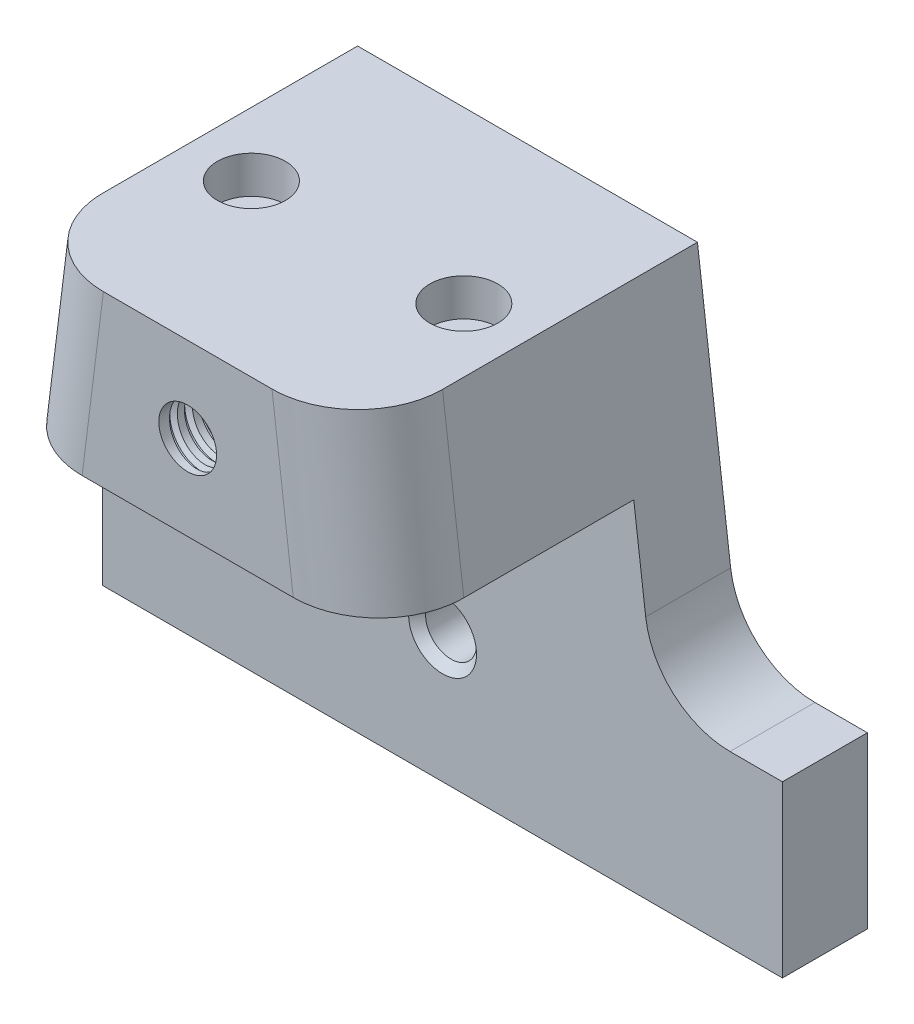
SolidWorks part; units mm, degrees
material "6063-T1"
ref_plane "Front" through (0, 0, 0) normal (0, 0, 1) x (1, 0, 0)
ref_plane "Top" through (0, 0, 0) normal (0, 1, 0) x (1, 0, 0)
ref_plane "Right" through (0, 0, 0) normal (1, 0, 0) x (0, 0, -1)
sketch "Schizzo4" plane through (0, 0, 0) normal (1, 0, 0) x (0, 0, -1)
  line L0 (0, 0) -> (-10, 0)
  line L1 (-10, 0) -> (-10, 40)
  line L2 (-10, 40) -> (-40, 40)
  line L3 (-40, 40) -> (-40, 60)
  line L4 (-40, 60) -> (0, 60)
  line L5 (0, 60) -> (0, 0)
  dimension "D1" = 10
  dimension "D2" = 40
  dimension "D3" = 30
  dimension "D4" = 20
extrude "Estrusione-Estrusione2" add sketch "Schizzo4" along normal mid plane 80
sketch "Schizzo5" plane through (0, 0, 40) normal (0, 0, 1) x (1, 0, 0)
  line L0 (-40, 20) -> (-25, 20)
  line L1 (-40, 40) -> (-40, 0) construction
  line L2 (-25, 20) -> (-20, 60)
  line L3 (40, 60) -> (-40, 60) construction
  line L4 (-20, 60) -> (20, 60)
  line L5 (20, 60) -> (25, 20)
  line L6 (25, 20) -> (40, 20)
  line L7 (40, 40) -> (40, 0) construction
  line L8 (0, 0) -> (0, 69.0809) construction
  line L9 (40, 0) -> (-40, 0) construction
  line L10 (-40, 20) -> (-40, 0)
  line L11 (-40, 0) -> (40, 0)
  line L12 (40, 0) -> (40, 20)
  dimension "D1" = 40
  dimension "D2" = 15
  dimension "D3" = 20
extrude "Taglio-Estrusione1" cut sketch "Schizzo5" against normal through all flip side to cut
fillet "Raccordo1" radius 10 2 edges at (-25, 20, 5) (25, 20, 5)
fillet "Raccordo2" radius 10 2 edges at (21.25, 50, 40) (-21.25, 50, 40)
hole_wizard "Foro filettato M4-2" positions "Schizzo6" profile "Schizzo8" tap size "M4" standard "ISO"
sketch "Schizzo6" plane through (0, 0, 0) normal (0, -1, 0) x (-1, 0, 0)
  line L0 (40, -5) -> (-40, -5) construction
  line L1 (40, -10) -> (40, 0) construction
  line L2 (-40, -10) -> (-40, 0) construction
  point P0 (-25, -5)
  point P2 (25, -5)
  dimension "D1" = 25
  dimension "D2" = 25
sketch "Schizzo8" plane through (25, 0, 5) normal (1, 0, 0) x (0, 0, -1)
  line L0 (0, 0) -> (0, 19.4914)
  line L1 (0, 19.4914) -> (1.65, 18.5)
  line L2 (1.65, 18.5) -> (1.65, 0)
  line L5 (1.65, 0) -> (0, 0)
  line L10 (0, 19.4914) -> (-1.65, 18.5) construction
  line L11 (0, -6.35) -> (0, 107.95) construction
  dimension "Tap Drill Dia." = 3.3
  dimension "Tap Drill Depth" = 18.5
  dimension "Drill Angle" = 118
cosmetic thread "Filettatura del foro3"
cosmetic thread "Filettatura del foro4"
hole_wizard "Foro lamato per Vite M4 a testa cilindrica-1" positions "Schizzo9" profile "Schizzo10" counterbore size "M4" standard "ISO" end condition through all
sketch "Schizzo9" plane through (0, 60, 0) normal (0, 1, 0) x (1, 0, 0)
  line L0 (22.5, -10) -> (-22.5, -10) construction
  line L1 (22.5, -10) -> (-22.5, -10)
  line L2 (0, 0) -> (0, -54.681) construction
  line L3 (20, 0) -> (-20, 0) construction
  point P0 (-12.5, -20)
  point P2 (12.5, -20)
  dimension "D1" = 10
  dimension "D2" = 25
sketch "Schizzo10" plane through (-12.5, 60, 20) normal (1, 0, 0) x (0, 0, 1)
  line L0 (0, 0) -> (0, 60)
  line L1 (0, 60) -> (2.25, 60)
  line L3 (2.25, 60) -> (2.25, 4.4)
  line L4 (2.25, 4.4) -> (4, 4.4)
  line L5 (4, 4.4) -> (4, 0)
  line L7 (4, 0) -> (0, 0)
  line L11 (0, -6.35) -> (0, 107.95) construction
  dimension "Thru Hole Dia." = 4.5
  dimension "Thru Hole Depth" = 60
  dimension "C'Bore Dia." = 8
  dimension "C'Bore Depth" = 4.4
hole_wizard "Foro filettato M8-1" positions "Schizzo11" profile "Schizzo12" tap size "M8" standard "ISO" end condition through all
sketch "Schizzo11" plane through (0, 0, 40) normal (0, 0, 1) x (1, 0, 0)
  line L0 (0, 0) -> (0, 92.6551) construction
  line L2 (12.4222, 40) -> (-12.4222, 40) construction
  point P0 (0, 50)
  dimension "D1" = 10
sketch "Schizzo12" plane through (0, 50, 40) normal (1, 0, 0) x (0, -1, 0)
  line L0 (0, 0) -> (0, 40)
  line L1 (0, 40) -> (3.4, 40)
  line L2 (3.4, 40) -> (3.4, 0)
  line L5 (3.4, 0) -> (0, 0)
  line L11 (0, -6.35) -> (0, 107.95) construction
  dimension "Thru Tap Drill Dia." = 6.8
  dimension "Thru Tap Drill Depth" = 40
cosmetic thread "Filettatura del foro5"
sketch "Schizzo14" plane through (0, 0, 10) normal (0, 0, 1) x (1, 0, 0)
  circle A0 centre (0, 15) radius 3
  dimension "D1" = 6
  dimension "D2" = 15
extrude "Taglio-Estrusione2" cut sketch "Schizzo14" against normal through all
chamfer "Smusso1" distance 1 angle 45 1 edges at (3, 15, 10)
thread "螺纹线1" pitch 1.0583 method cut profile "螺纹线轮廓1" start angle 0, offset 0, length 38.7, pitch 1.7583, diameter 6.8
ref_plane "基准面1" through (3.4, 50, 0) normal (0, 1, 0) x (-1, 0, 0)
sketch "螺纹线轮廓1" plane through (3.4, 50, 0) normal (0, 1, 0) x (-1, 0, 0)
  line L0 (0, 0) -> (0, 1.0583) construction
  line L11 (0, 0) -> (0, 0.926)
  line L12 (0, 0.926) -> (-0.5728, 0.5953)
  line L13 (-0.5728, 0.5953) -> (-0.5728, 0.3307)
  line L15 (-0.5728, 0.3307) -> (0, 0)
  line L17 (-0.5728, 0.463) -> (0, 0.463) construction
  point P2 (0, 0)
  dimension "Pitch" = 1.0583
  dimension "Profile_Angle" = 60
  dimension "Profile_Land" = 0.2646
  dimension "Profile_Height" = 0.5728
thread "螺纹线3" pitch 1.0583 method cut profile "螺纹线轮廓3" start angle 0, offset 0, length 17.4, pitch 1.4583, diameter 3.3
ref_plane "基准面3" through (26.65, 0, 5) normal (0, 0, -1) x (-1, 0, 0)
sketch "螺纹线轮廓3" plane through (26.65, 0, 5) normal (0, 0, -1) x (-1, 0, 0)
  line L0 (0, 0) -> (0, 1.0583) construction
  line L11 (0, 0) -> (0, 0.926)
  line L12 (0, 0.926) -> (-0.5728, 0.5953)
  line L13 (-0.5728, 0.5953) -> (-0.5728, 0.3307)
  line L15 (-0.5728, 0.3307) -> (0, 0)
  line L17 (-0.5728, 0.463) -> (0, 0.463) construction
  point P2 (0, 0)
  dimension "Pitch" = 1.0583
  dimension "Profile_Angle" = 60
  dimension "Profile_Land" = 0.2646
  dimension "Profile_Height" = 0.5728
thread "螺纹线4" pitch 1.0583 method cut profile "螺纹线轮廓4" start angle 0, offset 0, length 17.4, pitch 1.4583, diameter 3.3
ref_plane "基准面4" through (-23.35, 0, 5) normal (0, 0, -1) x (-1, 0, 0)
sketch "螺纹线轮廓4" plane through (-23.35, 0, 5) normal (0, 0, -1) x (-1, 0, 0)
  line L0 (0, 0) -> (0, 1.0583) construction
  line L11 (0, 0) -> (0, 0.926)
  line L12 (0, 0.926) -> (-0.5728, 0.5953)
  line L13 (-0.5728, 0.5953) -> (-0.5728, 0.3307)
  line L15 (-0.5728, 0.3307) -> (0, 0)
  line L17 (-0.5728, 0.463) -> (0, 0.463) construction
  point P2 (0, 0)
  dimension "Pitch" = 1.0583
  dimension "Profile_Angle" = 60
  dimension "Profile_Land" = 0.2646
  dimension "Profile_Height" = 0.5728
